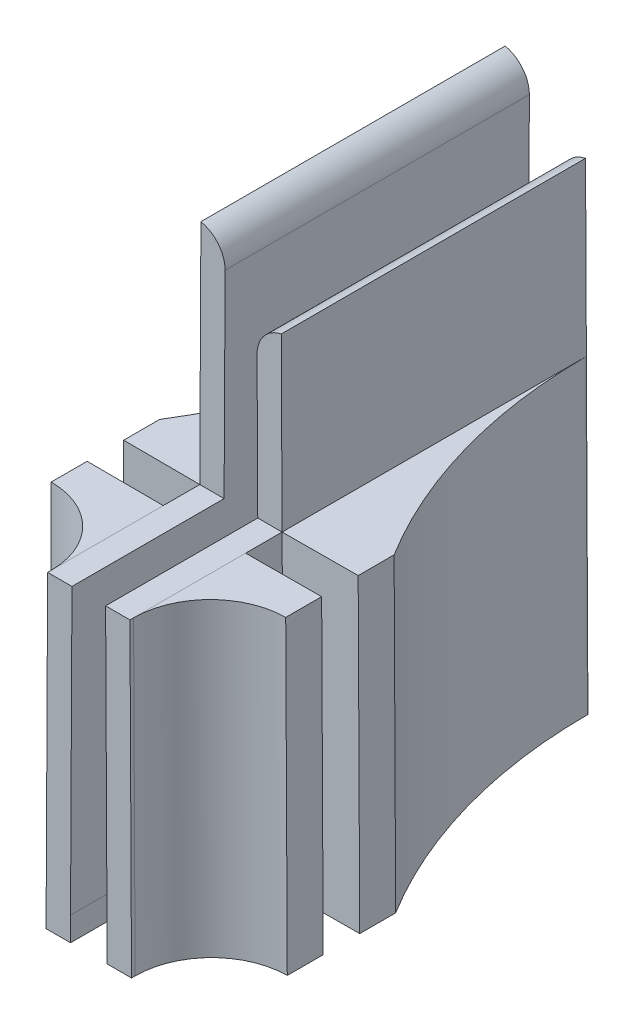
SolidWorks part; units mm, degrees
ref_plane "Front Plane" through (0, 0, 0) normal (0, 0, 1) x (1, 0, 0)
ref_plane "Top Plane" through (0, 0, 0) normal (0, 1, 0) x (1, 0, 0)
ref_plane "Right Plane" through (0, 0, 0) normal (1, 0, 0) x (0, 0, -1)
sketch "Sketch1" plane through (0, 0, 0) normal (0, 0, 1) x (1, 0, 0)
  line L0 (-3.566, 0) -> (3.566, 0)
  line L1 (3.566, 0) -> (3.3655, 40.1097)
  line L2 (3.3655, 40.1097) -> (1.3335, 40.0995)
  line L3 (1.3335, 40.0995) -> (1.524, 2)
  line L4 (1.524, 2) -> (-1.524, 2)
  line L5 (-1.524, 2) -> (-1.3335, 40.0995)
  line L6 (-1.3335, 40.0995) -> (-3.3655, 40.1097)
  line L7 (-3.3655, 40.1097) -> (-3.566, 0)
  line L8 (-3.3655, 40.1097) -> (-3.3417, 44.8721)
  line L9 (-3.3417, 44.8721) -> (-1.3097, 44.862)
  line L10 (-1.3097, 44.862) -> (-1.3335, 40.0995)
  point P11 (0, 0)
  point P13 (0, 2)
  dimension "D1" = 3.048
  dimension "D2" = 2.667
  dimension "D3" = 38.1
  dimension "D4" = 2.032
  dimension "D5" = 2
  dimension "D6" = 4.7625
extrude "Boss-Extrude1" add sketch "Sketch1" along normal blind 38.1 contours L6 L7 L0 L1 L2 L3 L4 L5 | L10 L9 L8 L6 region at (-3.0584, 20.0528, 0) region at (-2.3376, 42.4858, 0)
fillet "Fillet1" radius 2.54 2 edges at (1.3335, 40.0995, 19.05) (-1.3097, 44.862, 19.05)
sketch "Sketch2" plane through (0, 0, 38.1) normal (0, 0, 1) x (1, 0, 0)
  line L0 (-3.566, 0) -> (3.566, 0) construction
  line L1 (-1.524, 2) -> (1.524, 2)
  line L2 (-1.524, 2) -> (-1.524, 0)
  line L3 (-1.524, 0) -> (1.524, 0)
  line L4 (1.524, 2) -> (1.524, 0)
  line L5 (3.566, 0) -> (3.3655, 40.1097) construction
  line L6 (3.4369, 25.8221) -> (-3.4369, 25.8221)
  line L7 (3.4369, 25.8221) -> (3.4369, 44.8721)
  line L8 (3.4369, 44.8721) -> (-3.4369, 44.8721)
  line L9 (-3.4369, 25.8221) -> (-3.4369, 44.8721)
  line L10 (-3.3417, 44.8721) -> (-3.566, 0) construction
  point P14 (-3.4115, 21.2792)
  point P17 (0, 0)
  point P18 (-3.3297, 32.3748)
  point P19 (-3.4607, 32.734)
  dimension "D1" = 19.05
extrude "Cut-Extrude1" cut sketch "Sketch2" against normal blind 12.7
sketch "Sketch3" plane through (3.5659, 0.0178, 0) normal (1, 0.005, 0) x (0, 0, -1)
  line L0 (-25.4, 25.8046) -> (-38.1, 25.8046) construction
  line L1 (-25.4, 25.8046) -> (-22.4, 25.8046)
  line L2 (-25.4, 25.8046) -> (-25.4, -0.0178)
  line L3 (-25.4, -0.0178) -> (-22.4, -0.0178)
  line L4 (-22.4, 25.8046) -> (-22.4, -0.0178)
  line L5 (-28.448, 25.8046) -> (-31.448, 25.8046)
  line L6 (-28.448, 25.8046) -> (-28.448, -0.0178)
  line L7 (-28.448, -0.0178) -> (-31.448, -0.0178)
  line L8 (-31.448, 25.8046) -> (-31.448, -0.0178)
  line L9 (-38.1, -0.0178) -> (0, -0.0178) construction
  point P11 (-35.8401, 25.8046)
  point P12 (-22.4, -0.0178)
  dimension "D1" = 3.048
  dimension "D2" = 3
extrude "Boss-Extrude2" add sketch "Sketch3" along normal blind 6.35
sketch "Sketch4" plane through (-3.5659, 0.0178, 0) normal (-1, 0.005, 0) x (0, 0, 1)
  line L0 (38.1, -0.0178) -> (0, -0.0178) construction
  line L1 (31.448, -0.0178) -> (28.448, -0.0178)
  line L2 (31.448, -0.0178) -> (31.448, 25.8046)
  line L3 (31.448, 25.8046) -> (28.448, 25.8046)
  line L4 (28.448, -0.0178) -> (28.448, 25.8046)
  line L5 (31.448, 25.839) -> (31.448, 0.0178) construction
  line L6 (22.4, -0.0178) -> (25.4, -0.0178)
  line L7 (22.4, -0.0178) -> (22.4, 25.8046)
  line L8 (22.4, 25.8046) -> (25.4, 25.8046)
  line L9 (25.4, -0.0178) -> (25.4, 25.8046)
  line L10 (25.4, 25.839) -> (25.4, 0.0178) construction
  line L11 (22.4, 0.0178) -> (22.4, 25.839) construction
  line L12 (25.4, 25.8046) -> (38.1, 25.8046) construction
  point P16 (28.448, 25.5399)
  point P17 (28.448, 25.8046)
  point P20 (25.4, 25.8046)
extrude "Boss-Extrude4" add sketch "Sketch4" along normal blind 6.35
fillet "Fillet3" radius 42.545 2 edges at (3.5015, 12.9111, 22.4) (-3.5015, 12.9111, 22.4)
fillet "Fillet4" radius 6.35 2 edges at (3.5015, 12.9111, 31.448) (-3.5015, 12.9111, 31.448)
equation "\"bottomThickness\"= .220in"
equation "\"wallThickness\"= .125in"
equation "\"D2@Sketch1\"=\"wallThickness\"-.02in"
equation "\"D1@Sketch1\"=\"wallThickness\"-.005in"
